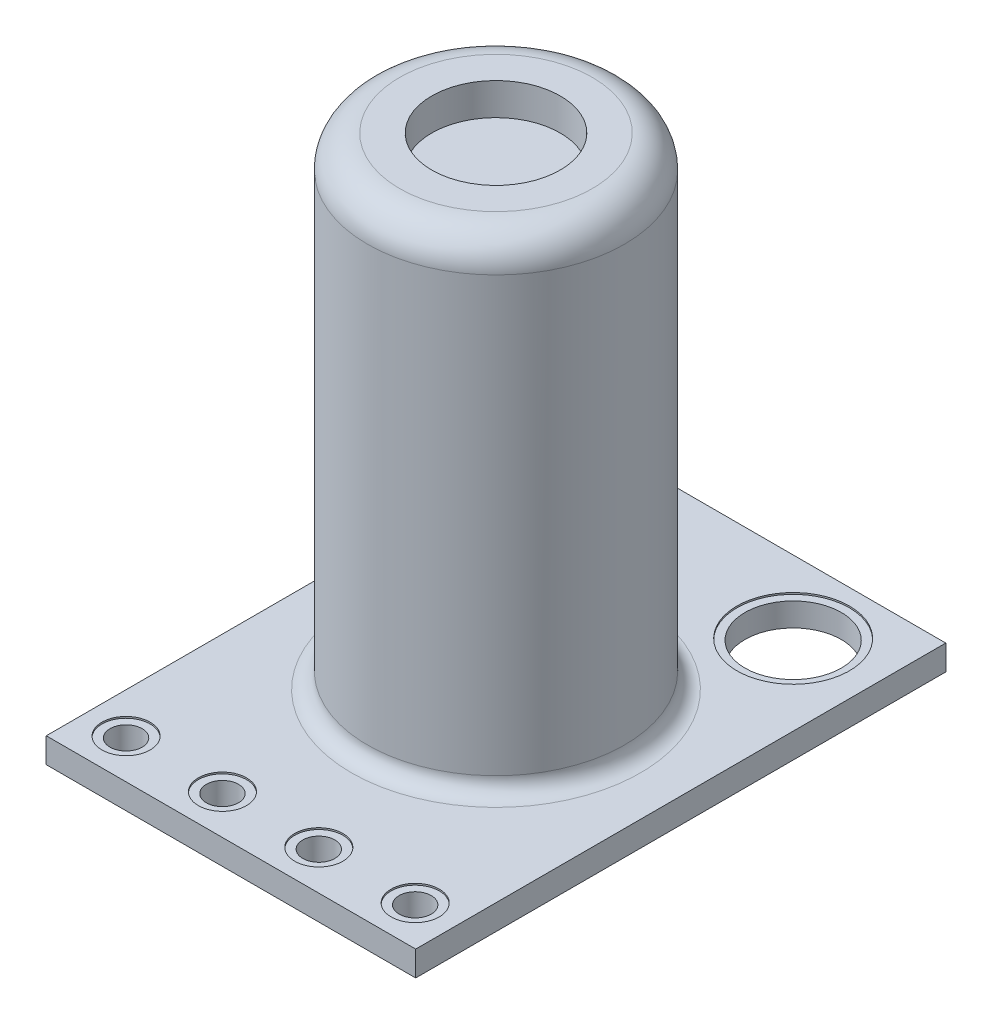
SolidWorks part; units mm, degrees
ref_plane "Front Plane" through (0, 0, 0) normal (0, 0, 1) x (1, 0, 0)
ref_plane "Top Plane" through (0, 0, 0) normal (0, 1, 0) x (1, 0, 0)
ref_plane "Right Plane" through (0, 0, 0) normal (1, 0, 0) x (0, 0, -1)
sketch "Sketch1" plane through (0, 0, 0) normal (0, 1, 0) x (1, 0, 0)
  line L1 (-5.75, -8.25) -> (5.75, -8.25)
  line L2 (-5.75, -8.25) -> (-5.75, 8.25)
  line L3 (-5.75, 8.25) -> (5.75, 8.25)
  line L4 (5.75, -8.25) -> (5.75, 8.25)
  line L5 (-5.75, -8.25) -> (5.75, 8.25) construction
  line L6 (-5.75, 8.25) -> (5.75, -8.25) construction
  point P0 (0, 0)
  dimension "D1" = 11.5
  dimension "D2" = 16.5
extrude "Boss-Extrude1" add sketch "Sketch1" along normal blind 0.78
sketch "Sketch2" plane through (0, 0.78, 0) normal (0, 1, 0) x (1, 0, 0)
  line L0 (0, 8.25) -> (0, -8.25) construction
  line L1 (5.75, 8.25) -> (-5.75, 8.25) construction
  line L2 (-5.75, -8.25) -> (5.75, -8.25) construction
  line L3 (-5.75, 8.25) -> (-5.75, -8.25) construction
  circle A0 centre (-4.5, -7.0156) radius 0.75
  circle A1 centre (-1.5, -7.0156) radius 0.75
  circle A2 centre (4.5, -7.0156) radius 0.75
  circle A3 centre (1.5, -7.0156) radius 0.75
  circle A4 centre (-4.5, -7.0156) radius 0.5
  circle A5 centre (-1.5, -7.0156) radius 0.5
  circle A6 centre (1.5, -7.0156) radius 0.5
  circle A7 centre (4.5, -7.0156) radius 0.5
  circle A8 centre (-3.25, 6) radius 1.75
  circle A9 centre (-3.25, 6) radius 1.5
  circle A10 centre (3.25, 6) radius 1.75
  circle A11 centre (3.25, 6) radius 1.5
  dimension "D1" = 1.5
  dimension "D4" = 1
  dimension "D5" = 3.5
  dimension "D8" = 3
  dimension "D2" = 1.5
  dimension "D3" = 3
  dimension "D6" = 2.5
  dimension "D7" = 2.25
extrude "Cut-Extrude1" cut sketch "Sketch2" against normal through all contours A4 | A5 | A6 | A7 | A9 | A11 | A4 region at (-4.5, 0.78, 7.0156) region at (-1.5, 0.78, 7.0156) region at (1.5, 0.78, 7.0156) region at (4.5, 0.78, 7.0156) region at (-3.25, 0.78, -6) region at (3.25, 0.78, -6)
extrude "Cut-Extrude2" cut sketch "Sketch2<3>" against normal blind 0.05
sketch "Sketch2<3>" plane through (0, 0.78, 0) normal (0, 1, 0) x (1, 0, 0) same geometry as "Sketch2"
sketch "Sketch4" plane through (0, 0.78, 0) normal (0, 1, 0) x (1, 0, 0)
  circle A0 centre (0, 0) radius 4
  dimension "D1" = 8
extrude "Boss-Extrude2" add sketch "Sketch4" along normal blind 15
fillet "Fillet1" radius 1 1 edges at (0, 15.78, 4)
fillet "Fillet2" radius 0.5 1 edges at (0, 0.78, -4)
sketch "Sketch5" plane through (0, 15.78, 0) normal (0, 1, 0) x (1, 0, 0)
  circle A2 centre (0, 0) radius 2
  circle A3 centre (0, 0) radius 2
  dimension "D1" = 1
extrude "Cut-Extrude3" cut sketch "Sketch5" against normal blind 1
